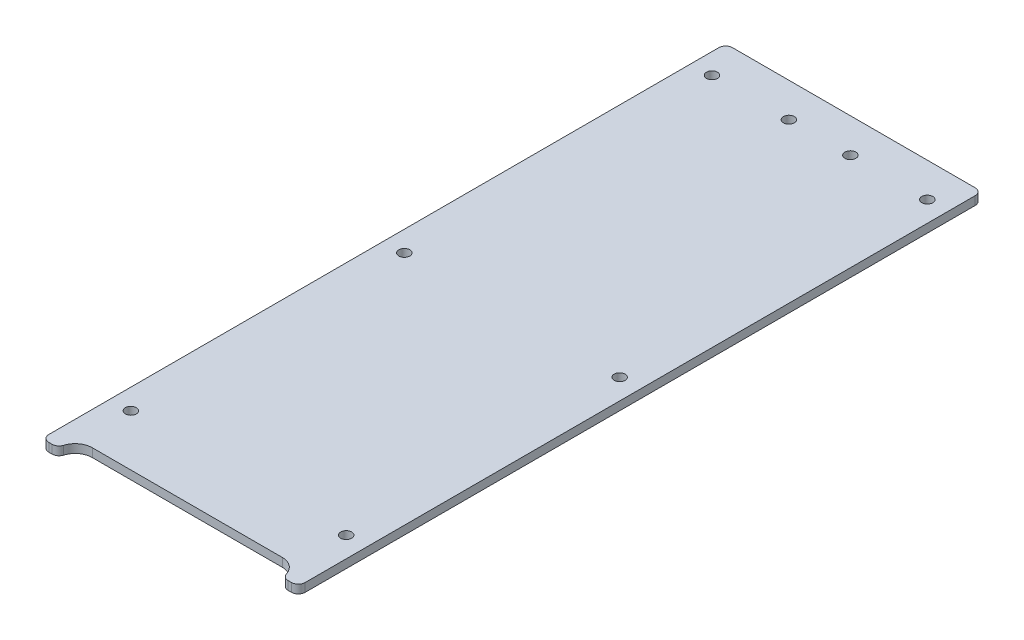
SolidWorks part; units mm, degrees
ref_plane "Front Plane" through (0, 0, 0) normal (0, 0, 1) x (1, 0, 0)
ref_plane "Top Plane" through (0, 0, 0) normal (0, 1, 0) x (1, 0, 0)
ref_plane "Right Plane" through (0, 0, 0) normal (1, 0, 0) x (0, 0, -1)
sketch "Sketch1" plane through (0, 0, 0) normal (0, 1, 0) x (1, 0, 0)
  line L0 (-39.9997, 0) -> (-39.9997, 114.3) construction
  line L1 (-47.625, 127) -> (47.625, 127)
  line L2 (-47.625, 127) -> (-47.625, -127)
  line L3 (-47.625, -127) -> (47.625, -127)
  line L4 (47.625, 127) -> (47.625, -127)
  line L5 (-47.625, 127) -> (47.625, -127) construction
  line L6 (-47.625, -127) -> (47.625, 127) construction
  line L7 (0, 0) -> (0, 127) construction
  line L8 (-39.9997, 0) -> (-39.9997, -101.6) construction
  line L9 (-39.9997, 0) -> (0, 0) construction
  line L10 (-41.275, -127) -> (-41.275, -120.65)
  line L11 (-41.275, -120.65) -> (41.275, -120.65)
  line L12 (41.275, -120.65) -> (41.275, -127)
  line L13 (-39.9997, 114.3) -> (-11.4247, 114.3) construction
  line L14 (39.9997, 114.3) -> (11.4247, 114.3) construction
  circle A0 centre (-39.9997, 114.3) radius 2.032
  circle A1 centre (-39.9997, 0) radius 2.032
  circle A2 centre (-39.9997, -101.6) radius 2.032
  circle A3 centre (39.9997, -101.6) radius 2.032
  circle A4 centre (39.9997, 0) radius 2.032
  circle A5 centre (39.9997, 114.3) radius 2.032
  circle A6 centre (-11.4247, 114.3) radius 2.032
  circle A7 centre (11.4247, 114.3) radius 2.032
  point P0 (0, 0)
  dimension "D4" = 4.064
  dimension "D10" = 28.575
  dimension "D1" = 95.25
  dimension "D2" = 254
  dimension "D3" = 7.6253
  dimension "D5" = 12.7
  dimension "D6" = 25.4
  dimension "D7" = 6.35
  dimension "D8" = 6.35
  dimension "D9" = 6.35
extrude "Boss-Extrude1" add sketch "Sketch1" along normal blind 3.175 contours L4 L1 L2 L3 A4 A0 A1 A2 A3 A5 region at (0, 0, -2.6146)
fillet "Fillet1" radius 2.54 4 edges at (-47.625, 1.5875, -127) (47.625, 1.5875, -127) (47.625, 1.5875, 127) (-47.625, 1.5875, 127)
fillet "Fillet2" radius 2.54 2 edges at (41.275, 1.5875, 127) (-41.275, 1.5875, 127)
fillet "Fillet3" radius 6.35 2 edges at (41.275, 1.5875, 120.65) (-41.275, 1.5875, 120.65)
